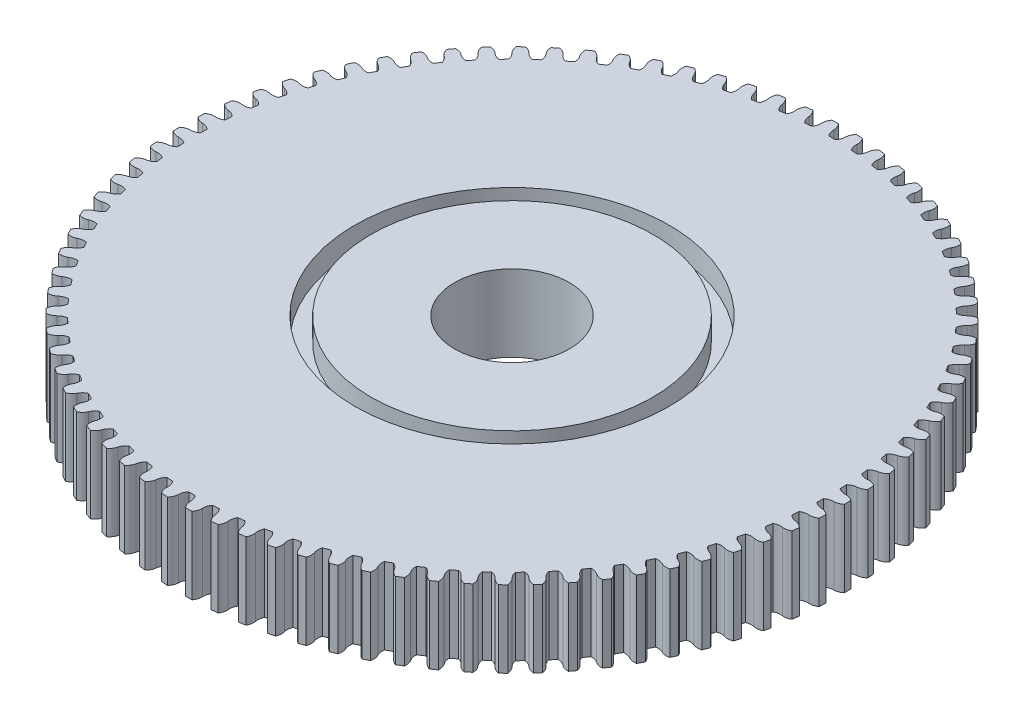
SolidWorks part; units mm, degrees
material "AISI 304"
ref_plane "Alzado" through (0, 0, 0) normal (0, 0, 1) x (1, 0, 0)
ref_plane "Planta" through (0, 0, 0) normal (0, 1, 0) x (1, 0, 0)
ref_plane "Vista lateral" through (0, 0, 0) normal (1, 0, 0) x (0, 0, -1)
sketch "Croquis1" plane through (0, 0, 0) normal (0, 1, 0) x (1, 0, 0)
  circle A0 centre (0, 0) radius 43
  dimension "D1" = 86
extrude "Saliente-Extruir1" add sketch "Croquis1" along normal blind 10
sketch "Croquis2" plane through (0, 10, 0) normal (0, 1, 0) x (1, 0, 0)
  line L0 (0, 0) -> (0, 42) construction
  arc A0 (1.9901, 42.9539) -> (-0.3825, 42.9983) centre (0, 0) ccw
  arc A2 (1.1967, 40.9825) -> (0.3366, 40.9986) centre (0, 0) ccw
  arc A3 (0, 42) -> (-0.3825, 42.9983) centre (-1.5705, 41.9706) ccw
  arc A5 (0, 42) -> (0.3366, 40.9986) centre (1.5705, 41.9706) ccw
  arc A6 (1.9901, 42.9539) -> (1.5705, 41.9706) centre (3.1388, 41.8825) ccw
  arc A7 (5.1945, 42.6851) -> (2.8318, 42.9067) centre (0, 0) ccw
  arc A8 (1.1967, 40.9825) -> (1.5705, 41.9706) centre (0, 42) ccw
  arc A9 (3.1387, 41.8826) -> (2.8318, 42.9067) centre (1.5703, 41.9706) ccw
  arc A10 (3.1387, 41.8826) -> (3.3995, 40.8588) centre (4.7026, 41.7359) ccw
  arc A11 (4.256, 40.7785) -> (3.3995, 40.8588) centre (0, 0) ccw
  arc A12 (4.256, 40.7785) -> (4.7026, 41.7359) centre (3.1387, 41.8826) ccw
  arc A13 (5.1945, 42.6851) -> (4.7026, 41.7359) centre (6.26, 41.5309) ccw
  arc A14 (8.3698, 42.1775) -> (6.0303, 42.5751) centre (0, 0) ccw
  arc A15 (6.2598, 41.5309) -> (6.0303, 42.5751) centre (4.7024, 41.7359) ccw
  arc A16 (6.2598, 41.5309) -> (6.4434, 40.4905) centre (7.8084, 41.2678) ccw
  arc A17 (7.2915, 40.3464) -> (6.4434, 40.4905) centre (0, 0) ccw
  arc A18 (7.2915, 40.3464) -> (7.8084, 41.2678) centre (6.2598, 41.5309) ccw
  arc A19 (8.3698, 42.1775) -> (7.8084, 41.2678) centre (9.3461, 40.9469) ccw
  arc A20 (11.4984, 41.4341) -> (9.1951, 42.0054) centre (0, 0) ccw
  arc A21 (9.3459, 40.947) -> (9.1951, 42.0054) centre (7.8082, 41.2678) ccw
  arc A22 (9.3459, 40.947) -> (9.4512, 39.8958) centre (10.8705, 40.5689) ccw
  arc A23 (10.2862, 39.6887) -> (9.4512, 39.8958) centre (0, 0) ccw
  arc A24 (10.2862, 39.6887) -> (10.8705, 40.5689) centre (9.3459, 40.947) ccw
  arc A25 (11.4984, 41.4341) -> (10.8705, 40.5689) centre (12.3799, 40.134) ccw
  arc A26 (14.5626, 40.459) -> (12.3084, 41.2008) centre (0, 0) ccw
  arc A27 (12.3797, 40.1341) -> (12.3084, 41.2008) centre (10.8703, 40.5689) ccw
  arc A28 (12.3797, 40.1341) -> (12.4062, 39.078) centre (13.8718, 39.6431) ccw
  arc A29 (13.2234, 38.8091) -> (12.4062, 39.078) centre (0, 0) ccw
  arc A30 (13.2234, 38.8091) -> (13.8718, 39.6431) centre (12.3797, 40.1341) ccw
  arc A31 (14.5626, 40.459) -> (13.8718, 39.6431) centre (15.3445, 39.0966) ccw
  arc A32 (17.5454, 39.2576) -> (15.3529, 40.1657) centre (0, 0) ccw
  arc A33 (15.3443, 39.0967) -> (15.3529, 40.1657) centre (13.8716, 39.6431) ccw
  arc A34 (15.3443, 39.0967) -> (15.2918, 38.0416) centre (16.7955, 38.4956) ccw
  arc A35 (16.0866, 37.7123) -> (15.2918, 38.0416) centre (0, 0) ccw
  arc A36 (16.0866, 37.7123) -> (16.7955, 38.4956) centre (15.3443, 39.0967) ccw
  arc A37 (17.5454, 39.2576) -> (16.7955, 38.4956) centre (18.2233, 37.8406) ccw
  arc A38 (20.4301, 37.8367) -> (18.3116, 38.9061) centre (0, 0) ccw
  arc A39 (18.2231, 37.8407) -> (18.3116, 38.9061) centre (16.7954, 38.4957) ccw
  arc A40 (18.2231, 37.8407) -> (18.0919, 36.7924) centre (19.6254, 37.1328) ccw
  arc A41 (18.8599, 36.4047) -> (18.0919, 36.7924) centre (0, 0) ccw
  arc A42 (18.8599, 36.4047) -> (19.6254, 37.1328) centre (18.2231, 37.8407) ccw
  arc A43 (20.4301, 37.8367) -> (19.6254, 37.1328) centre (21.0002, 36.373) ccw
  arc A44 (23.2005, 36.2041) -> (21.1679, 37.4289) centre (0, 0) ccw
  arc A45 (21, 36.3731) -> (21.1679, 37.4289) centre (19.6252, 37.1329) ccw
  arc A46 (21, 36.3731) -> (20.7908, 35.3376) centre (22.3454, 35.5624) ccw
  arc A47 (21.5277, 34.8935) -> (20.7908, 35.3376) centre (0, 0) ccw
  arc A48 (21.5277, 34.8935) -> (22.3454, 35.5624) centre (21, 36.3731) ccw
  arc A49 (23.2005, 36.2041) -> (22.3454, 35.5624) centre (23.6596, 34.7019) ccw
  arc A50 (25.8411, 34.3691) -> (23.9057, 35.7424) centre (0, 0) ccw
  arc A51 (23.6594, 34.702) -> (23.9057, 35.7424) centre (22.3453, 35.5625) ccw
  arc A52 (23.6594, 34.702) -> (23.3734, 33.685) centre (24.9405, 33.7931) ccw
  arc A53 (24.0751, 33.1872) -> (23.3734, 33.685) centre (0, 0) ccw
  arc A54 (24.0751, 33.1872) -> (24.9405, 33.7931) centre (23.6594, 34.702) ccw
  arc A55 (25.8411, 34.3691) -> (24.9405, 33.7931) centre (26.1867, 32.8368) ccw
  arc A56 (28.3373, 32.3419) -> (26.5099, 33.8559) centre (0, 0) ccw
  arc A57 (26.1866, 32.8369) -> (26.5099, 33.8559) centre (24.9404, 33.7932) ccw
  arc A58 (26.1866, 32.8369) -> (25.8254, 31.8442) centre (27.3961, 31.8348) ccw
  arc A59 (26.4878, 31.2953) -> (25.8254, 31.8442) centre (0, 0) ccw
  arc A60 (26.4878, 31.2953) -> (27.3961, 31.8348) centre (26.1866, 32.8369) ccw
  arc A61 (28.3373, 32.3419) -> (27.3961, 31.8348) centre (28.5674, 30.7881) ccw
  arc A62 (30.675, 30.1338) -> (28.9658, 31.7802) centre (0, 0) ccw
  arc A63 (28.5673, 30.7882) -> (28.9658, 31.7802) centre (27.396, 31.8349) ccw
  arc A64 (28.5673, 30.7882) -> (28.1329, 29.8252) centre (29.6985, 29.6984) ccw
  arc A65 (28.7525, 29.2283) -> (28.1329, 29.8252) centre (0, 0) ccw
  arc A66 (28.7525, 29.2283) -> (29.6985, 29.6984) centre (28.5673, 30.7882) ccw
  arc A67 (30.675, 30.1338) -> (29.6985, 29.6984) centre (30.7883, 28.5671) ccw
  arc A68 (32.8411, 27.7572) -> (31.2598, 29.5267) centre (0, 0) ccw
  arc A69 (30.7882, 28.5673) -> (31.2598, 29.5267) centre (29.6984, 29.6985) ccw
  arc A70 (30.7882, 28.5673) -> (30.283, 27.6394) centre (31.8349, 27.396) ccw
  arc A71 (30.8563, 26.9979) -> (30.283, 27.6394) centre (0, 0) ccw
  arc A72 (30.8563, 26.9979) -> (31.8349, 27.396) centre (30.7882, 28.5673) ccw
  arc A73 (32.8411, 27.7572) -> (31.8349, 27.396) centre (32.837, 26.1864) ccw
  arc A74 (34.8236, 25.2254) -> (33.3789, 27.1081) centre (0, 0) ccw
  arc A75 (32.8369, 26.1866) -> (33.3789, 27.1081) centre (31.8348, 27.3961) ccw
  arc A76 (32.8369, 26.1866) -> (32.2639, 25.2991) centre (33.7932, 24.9404) ccw
  arc A77 (32.7876, 24.6166) -> (32.2639, 25.2991) centre (0, 0) ccw
  arc A78 (32.7876, 24.6166) -> (33.7932, 24.9404) centre (32.8369, 26.1866) ccw
  arc A79 (34.8236, 25.2254) -> (33.7932, 24.9404) centre (34.7021, 23.6593) ccw
  arc A80 (36.6113, 22.5525) -> (35.3114, 24.5379) centre (0, 0) ccw
  arc A81 (34.702, 23.6594) -> (35.3114, 24.5379) centre (33.7931, 24.9405) ccw
  arc A82 (34.702, 23.6594) -> (34.0643, 22.8172) centre (35.5625, 22.3453) ccw
  arc A83 (34.5355, 22.0975) -> (34.0643, 22.8172) centre (0, 0) ccw
  arc A84 (34.5355, 22.0975) -> (35.5625, 22.3453) centre (34.702, 23.6594) ccw
  arc A85 (36.6113, 22.5525) -> (35.5625, 22.3453) centre (36.3732, 20.9998) ccw
  arc A86 (38.1943, 19.7535) -> (37.0463, 21.8304) centre (0, 0) ccw
  arc A87 (36.3731, 21) -> (37.0463, 21.8304) centre (35.5624, 22.3454) ccw
  arc A88 (36.3731, 21) -> (35.6741, 20.2078) centre (37.1329, 19.6252) ccw
  arc A89 (36.0903, 19.4549) -> (35.6741, 20.2078) centre (0, 0) ccw
  arc A90 (36.0903, 19.4549) -> (37.1329, 19.6252) centre (36.3731, 21) ccw
  arc A91 (38.1943, 19.7535) -> (37.1329, 19.6252) centre (37.8408, 18.223) ccw
  arc A92 (39.5636, 16.844) -> (38.5741, 19.0009) centre (0, 0) ccw
  arc A93 (37.8407, 18.2231) -> (38.5741, 19.0009) centre (37.1328, 19.6254) ccw
  arc A94 (37.8407, 18.2231) -> (37.0845, 17.4854) centre (38.4957, 16.7954) ccw
  arc A95 (37.4432, 16.7034) -> (37.0845, 17.4854) centre (0, 0) ccw
  arc A96 (37.4432, 16.7034) -> (38.4957, 16.7954) centre (37.8407, 18.2231) ccw
  arc A97 (39.5636, 16.844) -> (38.4957, 16.7954) centre (39.0968, 15.3442) ccw
  arc A98 (40.7118, 13.8403) -> (39.8862, 16.0651) centre (0, 0) ccw
  arc A99 (39.0967, 15.3443) -> (39.8862, 16.0651) centre (38.4956, 16.7955) ccw
  arc A100 (39.0967, 15.3443) -> (38.2875, 14.6652) centre (39.6431, 13.8716) ccw
  arc A101 (38.5868, 13.8586) -> (38.2875, 14.6652) centre (0, 0) ccw
  arc A102 (38.5868, 13.8586) -> (39.6431, 13.8716) centre (39.0967, 15.3443) ccw
  arc A103 (40.7118, 13.8403) -> (39.6431, 13.8716) centre (40.1341, 12.3795) ccw
  arc A104 (41.6322, 10.7592) -> (40.9752, 13.0395) centre (0, 0) ccw
  arc A105 (40.1341, 12.3797) -> (40.9752, 13.0395) centre (39.6431, 13.8718) ccw
  arc A106 (40.1341, 12.3797) -> (39.2764, 11.7629) centre (40.5689, 10.8703) ccw
  arc A107 (39.5145, 10.9363) -> (39.2764, 11.7629) centre (0, 0) ccw
  arc A108 (39.5145, 10.9363) -> (40.5689, 10.8703) centre (40.1341, 12.3797) ccw
  arc A109 (41.6322, 10.7592) -> (40.5689, 10.8703) centre (40.947, 9.3457) ccw
  arc A110 (42.3198, 7.6179) -> (41.8351, 9.941) centre (0, 0) ccw
  arc A111 (40.947, 9.3459) -> (41.8351, 9.941) centre (40.5689, 10.8705) ccw
  arc A112 (40.947, 9.3459) -> (40.0456, 8.7949) centre (41.2678, 7.8082) ccw
  arc A113 (40.2213, 7.9527) -> (40.0456, 8.7949) centre (0, 0) ccw
  arc A114 (40.2213, 7.9527) -> (41.2678, 7.8082) centre (40.947, 9.3459) ccw
  arc A115 (42.3198, 7.6179) -> (41.2678, 7.8082) centre (41.5309, 6.2596) ccw
  arc A116 (42.7708, 4.4341) -> (42.461, 6.7868) centre (0, 0) ccw
  arc A117 (41.5309, 6.2598) -> (42.461, 6.7868) centre (41.2678, 7.8084) ccw
  arc A118 (41.5309, 6.2598) -> (40.5909, 5.7777) centre (41.7359, 4.7024) ccw
  arc A119 (40.7032, 4.9248) -> (40.5909, 5.7777) centre (0, 0) ccw
  arc A120 (40.7032, 4.9248) -> (41.7359, 4.7024) centre (41.5309, 6.2598) ccw
  arc A121 (42.7708, 4.4341) -> (41.7359, 4.7024) centre (41.8826, 3.1385) ccw
  arc A122 (42.9825, 1.2254) -> (42.8495, 3.5947) centre (0, 0) ccw
  arc A123 (41.8826, 3.1387) -> (42.8495, 3.5947) centre (41.7359, 4.7026) ccw
  arc A124 (41.8826, 3.1387) -> (40.9091, 2.7282) centre (41.9706, 1.5703) ccw
  arc A125 (40.9574, 1.8692) -> (40.9091, 2.7282) centre (0, 0) ccw
  arc A126 (40.9574, 1.8692) -> (41.9706, 1.5703) centre (41.8826, 3.1387) ccw
  arc A127 (42.9825, 1.2254) -> (41.9706, 1.5703) centre (42, -0.0002) ccw
  arc A128 (42.9539, -1.9901) -> (42.9983, 0.3825) centre (0, 0) ccw
  arc A129 (42, 0) -> (42.9983, 0.3825) centre (41.9706, 1.5705) ccw
  arc A130 (42, 0) -> (40.9986, -0.3366) centre (41.9706, -1.5705) ccw
  arc A131 (40.9825, -1.1967) -> (40.9986, -0.3366) centre (0, 0) ccw
  arc A132 (40.9825, -1.1967) -> (41.9706, -1.5705) centre (42, 0) ccw
  arc A133 (42.9539, -1.9901) -> (41.9706, -1.5705) centre (41.8825, -3.1388) ccw
  arc A134 (42.6851, -5.1945) -> (42.9067, -2.8318) centre (0, 0) ccw
  arc A135 (41.8826, -3.1387) -> (42.9067, -2.8318) centre (41.9706, -1.5703) ccw
  arc A136 (41.8826, -3.1387) -> (40.8588, -3.3995) centre (41.7359, -4.7026) ccw
  arc A137 (40.7785, -4.256) -> (40.8588, -3.3995) centre (0, 0) ccw
  arc A138 (40.7785, -4.256) -> (41.7359, -4.7026) centre (41.8826, -3.1387) ccw
  arc A139 (42.6851, -5.1945) -> (41.7359, -4.7026) centre (41.5309, -6.26) ccw
  arc A140 (42.1775, -8.3698) -> (42.5751, -6.0303) centre (0, 0) ccw
  arc A141 (41.5309, -6.2598) -> (42.5751, -6.0303) centre (41.7359, -4.7024) ccw
  arc A142 (41.5309, -6.2598) -> (40.4905, -6.4434) centre (41.2678, -7.8084) ccw
  arc A143 (40.3464, -7.2915) -> (40.4905, -6.4434) centre (0, 0) ccw
  arc A144 (40.3464, -7.2915) -> (41.2678, -7.8084) centre (41.5309, -6.2598) ccw
  arc A145 (42.1775, -8.3698) -> (41.2678, -7.8084) centre (40.9469, -9.3461) ccw
  arc A146 (41.4341, -11.4984) -> (42.0054, -9.1951) centre (0, 0) ccw
  arc A147 (40.947, -9.3459) -> (42.0054, -9.1951) centre (41.2678, -7.8082) ccw
  arc A148 (40.947, -9.3459) -> (39.8958, -9.4512) centre (40.5689, -10.8705) ccw
  arc A149 (39.6887, -10.2862) -> (39.8958, -9.4512) centre (0, 0) ccw
  arc A150 (39.6887, -10.2862) -> (40.5689, -10.8705) centre (40.947, -9.3459) ccw
  arc A151 (41.4341, -11.4984) -> (40.5689, -10.8705) centre (40.134, -12.3799) ccw
  arc A152 (40.459, -14.5626) -> (41.2008, -12.3084) centre (0, 0) ccw
  arc A153 (40.1341, -12.3797) -> (41.2008, -12.3084) centre (40.5689, -10.8703) ccw
  arc A154 (40.1341, -12.3797) -> (39.078, -12.4062) centre (39.6431, -13.8718) ccw
  arc A155 (38.8091, -13.2234) -> (39.078, -12.4062) centre (0, 0) ccw
  arc A156 (38.8091, -13.2234) -> (39.6431, -13.8718) centre (40.1341, -12.3797) ccw
  arc A157 (40.459, -14.5626) -> (39.6431, -13.8718) centre (39.0966, -15.3445) ccw
  arc A158 (39.2576, -17.5454) -> (40.1657, -15.3529) centre (0, 0) ccw
  arc A159 (39.0967, -15.3443) -> (40.1657, -15.3529) centre (39.6431, -13.8716) ccw
  arc A160 (39.0967, -15.3443) -> (38.0416, -15.2918) centre (38.4956, -16.7955) ccw
  arc A161 (37.7123, -16.0866) -> (38.0416, -15.2918) centre (0, 0) ccw
  arc A162 (37.7123, -16.0866) -> (38.4956, -16.7955) centre (39.0967, -15.3443) ccw
  arc A163 (39.2576, -17.5454) -> (38.4956, -16.7955) centre (37.8406, -18.2233) ccw
  arc A164 (37.8367, -20.4301) -> (38.9061, -18.3116) centre (0, 0) ccw
  arc A165 (37.8407, -18.2231) -> (38.9061, -18.3116) centre (38.4957, -16.7954) ccw
  arc A166 (37.8407, -18.2231) -> (36.7924, -18.0919) centre (37.1328, -19.6254) ccw
  arc A167 (36.4047, -18.8599) -> (36.7924, -18.0919) centre (0, 0) ccw
  arc A168 (36.4047, -18.8599) -> (37.1328, -19.6254) centre (37.8407, -18.2231) ccw
  arc A169 (37.8367, -20.4301) -> (37.1328, -19.6254) centre (36.373, -21.0002) ccw
  arc A170 (36.2041, -23.2005) -> (37.4289, -21.1679) centre (0, 0) ccw
  arc A171 (36.3731, -21) -> (37.4289, -21.1679) centre (37.1329, -19.6252) ccw
  arc A172 (36.3731, -21) -> (35.3376, -20.7908) centre (35.5624, -22.3454) ccw
  arc A173 (34.8935, -21.5277) -> (35.3376, -20.7908) centre (0, 0) ccw
  arc A174 (34.8935, -21.5277) -> (35.5624, -22.3454) centre (36.3731, -21) ccw
  arc A175 (36.2041, -23.2005) -> (35.5624, -22.3454) centre (34.7019, -23.6596) ccw
  arc A176 (34.3691, -25.8411) -> (35.7424, -23.9057) centre (0, 0) ccw
  arc A177 (34.702, -23.6594) -> (35.7424, -23.9057) centre (35.5625, -22.3453) ccw
  arc A178 (34.702, -23.6594) -> (33.685, -23.3734) centre (33.7931, -24.9405) ccw
  arc A179 (33.1872, -24.0751) -> (33.685, -23.3734) centre (0, 0) ccw
  arc A180 (33.1872, -24.0751) -> (33.7931, -24.9405) centre (34.702, -23.6594) ccw
  arc A181 (34.3691, -25.8411) -> (33.7931, -24.9405) centre (32.8368, -26.1867) ccw
  arc A182 (32.3419, -28.3373) -> (33.8559, -26.5099) centre (0, 0) ccw
  arc A183 (32.8369, -26.1866) -> (33.8559, -26.5099) centre (33.7932, -24.9404) ccw
  arc A184 (32.8369, -26.1866) -> (31.8442, -25.8254) centre (31.8348, -27.3961) ccw
  arc A185 (31.2953, -26.4878) -> (31.8442, -25.8254) centre (0, 0) ccw
  arc A186 (31.2953, -26.4878) -> (31.8348, -27.3961) centre (32.8369, -26.1866) ccw
  arc A187 (32.3419, -28.3373) -> (31.8348, -27.3961) centre (30.7881, -28.5674) ccw
  arc A188 (30.1338, -30.675) -> (31.7802, -28.9658) centre (0, 0) ccw
  arc A189 (30.7882, -28.5673) -> (31.7802, -28.9658) centre (31.8349, -27.396) ccw
  arc A190 (30.7882, -28.5673) -> (29.8252, -28.1329) centre (29.6984, -29.6985) ccw
  arc A191 (29.2283, -28.7525) -> (29.8252, -28.1329) centre (0, 0) ccw
  arc A192 (29.2283, -28.7525) -> (29.6984, -29.6985) centre (30.7882, -28.5673) ccw
  arc A193 (30.1338, -30.675) -> (29.6984, -29.6985) centre (28.5671, -30.7883) ccw
  arc A194 (27.7572, -32.8411) -> (29.5267, -31.2598) centre (0, 0) ccw
  arc A195 (28.5673, -30.7882) -> (29.5267, -31.2598) centre (29.6985, -29.6984) ccw
  arc A196 (28.5673, -30.7882) -> (27.6394, -30.283) centre (27.396, -31.8349) ccw
  arc A197 (26.9979, -30.8563) -> (27.6394, -30.283) centre (0, 0) ccw
  arc A198 (26.9979, -30.8563) -> (27.396, -31.8349) centre (28.5673, -30.7882) ccw
  arc A199 (27.7572, -32.8411) -> (27.396, -31.8349) centre (26.1864, -32.837) ccw
  arc A200 (25.2254, -34.8236) -> (27.1081, -33.3789) centre (0, 0) ccw
  arc A201 (26.1866, -32.8369) -> (27.1081, -33.3789) centre (27.3961, -31.8348) ccw
  arc A202 (26.1866, -32.8369) -> (25.2991, -32.2639) centre (24.9404, -33.7932) ccw
  arc A203 (24.6166, -32.7876) -> (25.2991, -32.2639) centre (0, 0) ccw
  arc A204 (24.6166, -32.7876) -> (24.9404, -33.7932) centre (26.1866, -32.8369) ccw
  arc A205 (25.2254, -34.8236) -> (24.9404, -33.7932) centre (23.6593, -34.7021) ccw
  arc A206 (22.5525, -36.6113) -> (24.5379, -35.3114) centre (0, 0) ccw
  arc A207 (23.6594, -34.702) -> (24.5379, -35.3114) centre (24.9405, -33.7931) ccw
  arc A208 (23.6594, -34.702) -> (22.8172, -34.0643) centre (22.3453, -35.5625) ccw
  arc A209 (22.0975, -34.5355) -> (22.8172, -34.0643) centre (0, 0) ccw
  arc A210 (22.0975, -34.5355) -> (22.3453, -35.5625) centre (23.6594, -34.702) ccw
  arc A211 (22.5525, -36.6113) -> (22.3453, -35.5625) centre (20.9998, -36.3732) ccw
  arc A212 (19.7535, -38.1943) -> (21.8304, -37.0463) centre (0, 0) ccw
  arc A213 (21, -36.3731) -> (21.8304, -37.0463) centre (22.3454, -35.5624) ccw
  arc A214 (21, -36.3731) -> (20.2078, -35.6741) centre (19.6252, -37.1329) ccw
  arc A215 (19.4549, -36.0903) -> (20.2078, -35.6741) centre (0, 0) ccw
  arc A216 (19.4549, -36.0903) -> (19.6252, -37.1329) centre (21, -36.3731) ccw
  arc A217 (19.7535, -38.1943) -> (19.6252, -37.1329) centre (18.223, -37.8408) ccw
  arc A218 (16.844, -39.5636) -> (19.0009, -38.5741) centre (0, 0) ccw
  arc A219 (18.2231, -37.8407) -> (19.0009, -38.5741) centre (19.6254, -37.1328) ccw
  arc A220 (18.2231, -37.8407) -> (17.4854, -37.0845) centre (16.7954, -38.4957) ccw
  arc A221 (16.7034, -37.4432) -> (17.4854, -37.0845) centre (0, 0) ccw
  arc A222 (16.7034, -37.4432) -> (16.7954, -38.4957) centre (18.2231, -37.8407) ccw
  arc A223 (16.844, -39.5636) -> (16.7954, -38.4957) centre (15.3442, -39.0968) ccw
  arc A224 (13.8403, -40.7118) -> (16.0651, -39.8862) centre (0, 0) ccw
  arc A225 (15.3443, -39.0967) -> (16.0651, -39.8862) centre (16.7955, -38.4956) ccw
  arc A226 (15.3443, -39.0967) -> (14.6652, -38.2875) centre (13.8716, -39.6431) ccw
  arc A227 (13.8586, -38.5868) -> (14.6652, -38.2875) centre (0, 0) ccw
  arc A228 (13.8586, -38.5868) -> (13.8716, -39.6431) centre (15.3443, -39.0967) ccw
  arc A229 (13.8403, -40.7118) -> (13.8716, -39.6431) centre (12.3795, -40.1341) ccw
  arc A230 (10.7592, -41.6322) -> (13.0395, -40.9752) centre (0, 0) ccw
  arc A231 (12.3797, -40.1341) -> (13.0395, -40.9752) centre (13.8718, -39.6431) ccw
  arc A232 (12.3797, -40.1341) -> (11.7629, -39.2764) centre (10.8703, -40.5689) ccw
  arc A233 (10.9363, -39.5145) -> (11.7629, -39.2764) centre (0, 0) ccw
  arc A234 (10.9363, -39.5145) -> (10.8703, -40.5689) centre (12.3797, -40.1341) ccw
  arc A235 (10.7592, -41.6322) -> (10.8703, -40.5689) centre (9.3457, -40.947) ccw
  arc A236 (7.6179, -42.3198) -> (9.941, -41.8351) centre (0, 0) ccw
  arc A237 (9.3459, -40.947) -> (9.941, -41.8351) centre (10.8705, -40.5689) ccw
  arc A238 (9.3459, -40.947) -> (8.7949, -40.0456) centre (7.8082, -41.2678) ccw
  arc A239 (7.9527, -40.2213) -> (8.7949, -40.0456) centre (0, 0) ccw
  arc A240 (7.9527, -40.2213) -> (7.8082, -41.2678) centre (9.3459, -40.947) ccw
  arc A241 (7.6179, -42.3198) -> (7.8082, -41.2678) centre (6.2596, -41.5309) ccw
  arc A242 (4.4341, -42.7708) -> (6.7868, -42.461) centre (0, 0) ccw
  arc A243 (6.2598, -41.5309) -> (6.7868, -42.461) centre (7.8084, -41.2678) ccw
  arc A244 (6.2598, -41.5309) -> (5.7777, -40.5909) centre (4.7024, -41.7359) ccw
  arc A245 (4.9248, -40.7032) -> (5.7777, -40.5909) centre (0, 0) ccw
  arc A246 (4.9248, -40.7032) -> (4.7024, -41.7359) centre (6.2598, -41.5309) ccw
  arc A247 (4.4341, -42.7708) -> (4.7024, -41.7359) centre (3.1385, -41.8826) ccw
  arc A248 (1.2254, -42.9825) -> (3.5947, -42.8495) centre (0, 0) ccw
  arc A249 (3.1387, -41.8826) -> (3.5947, -42.8495) centre (4.7026, -41.7359) ccw
  arc A250 (3.1387, -41.8826) -> (2.7282, -40.9091) centre (1.5703, -41.9706) ccw
  arc A251 (1.8692, -40.9574) -> (2.7282, -40.9091) centre (0, 0) ccw
  arc A252 (1.8692, -40.9574) -> (1.5703, -41.9706) centre (3.1387, -41.8826) ccw
  arc A253 (1.2254, -42.9825) -> (1.5703, -41.9706) centre (-0.0002, -42) ccw
  arc A254 (-1.9901, -42.9539) -> (0.3825, -42.9983) centre (0, 0) ccw
  arc A255 (0, -42) -> (0.3825, -42.9983) centre (1.5705, -41.9706) ccw
  arc A256 (0, -42) -> (-0.3366, -40.9986) centre (-1.5705, -41.9706) ccw
  arc A257 (-1.1967, -40.9825) -> (-0.3366, -40.9986) centre (0, 0) ccw
  arc A258 (-1.1967, -40.9825) -> (-1.5705, -41.9706) centre (0, -42) ccw
  arc A259 (-1.9901, -42.9539) -> (-1.5705, -41.9706) centre (-3.1388, -41.8825) ccw
  arc A260 (-5.1945, -42.6851) -> (-2.8318, -42.9067) centre (0, 0) ccw
  arc A261 (-3.1387, -41.8826) -> (-2.8318, -42.9067) centre (-1.5703, -41.9706) ccw
  arc A262 (-3.1387, -41.8826) -> (-3.3995, -40.8588) centre (-4.7026, -41.7359) ccw
  arc A263 (-4.256, -40.7785) -> (-3.3995, -40.8588) centre (0, 0) ccw
  arc A264 (-4.256, -40.7785) -> (-4.7026, -41.7359) centre (-3.1387, -41.8826) ccw
  arc A265 (-5.1945, -42.6851) -> (-4.7026, -41.7359) centre (-6.26, -41.5309) ccw
  arc A266 (-8.3698, -42.1775) -> (-6.0303, -42.5751) centre (0, 0) ccw
  arc A267 (-6.2598, -41.5309) -> (-6.0303, -42.5751) centre (-4.7024, -41.7359) ccw
  arc A268 (-6.2598, -41.5309) -> (-6.4434, -40.4905) centre (-7.8084, -41.2678) ccw
  arc A269 (-7.2915, -40.3464) -> (-6.4434, -40.4905) centre (0, 0) ccw
  arc A270 (-7.2915, -40.3464) -> (-7.8084, -41.2678) centre (-6.2598, -41.5309) ccw
  arc A271 (-8.3698, -42.1775) -> (-7.8084, -41.2678) centre (-9.3461, -40.9469) ccw
  arc A272 (-11.4984, -41.4341) -> (-9.1951, -42.0054) centre (0, 0) ccw
  arc A273 (-9.3459, -40.947) -> (-9.1951, -42.0054) centre (-7.8082, -41.2678) ccw
  arc A274 (-9.3459, -40.947) -> (-9.4512, -39.8958) centre (-10.8705, -40.5689) ccw
  arc A275 (-10.2862, -39.6887) -> (-9.4512, -39.8958) centre (0, 0) ccw
  arc A276 (-10.2862, -39.6887) -> (-10.8705, -40.5689) centre (-9.3459, -40.947) ccw
  arc A277 (-11.4984, -41.4341) -> (-10.8705, -40.5689) centre (-12.3799, -40.134) ccw
  arc A278 (-14.5626, -40.459) -> (-12.3084, -41.2008) centre (0, 0) ccw
  arc A279 (-12.3797, -40.1341) -> (-12.3084, -41.2008) centre (-10.8703, -40.5689) ccw
  arc A280 (-12.3797, -40.1341) -> (-12.4062, -39.078) centre (-13.8718, -39.6431) ccw
  arc A281 (-13.2234, -38.8091) -> (-12.4062, -39.078) centre (0, 0) ccw
  arc A282 (-13.2234, -38.8091) -> (-13.8718, -39.6431) centre (-12.3797, -40.1341) ccw
  arc A283 (-14.5626, -40.459) -> (-13.8718, -39.6431) centre (-15.3445, -39.0966) ccw
  arc A284 (-17.5454, -39.2576) -> (-15.3529, -40.1657) centre (0, 0) ccw
  arc A285 (-15.3443, -39.0967) -> (-15.3529, -40.1657) centre (-13.8716, -39.6431) ccw
  arc A286 (-15.3443, -39.0967) -> (-15.2918, -38.0416) centre (-16.7955, -38.4956) ccw
  arc A287 (-16.0866, -37.7123) -> (-15.2918, -38.0416) centre (0, 0) ccw
  arc A288 (-16.0866, -37.7123) -> (-16.7955, -38.4956) centre (-15.3443, -39.0967) ccw
  arc A289 (-17.5454, -39.2576) -> (-16.7955, -38.4956) centre (-18.2233, -37.8406) ccw
  arc A290 (-20.4301, -37.8367) -> (-18.3116, -38.9061) centre (0, 0) ccw
  arc A291 (-18.2231, -37.8407) -> (-18.3116, -38.9061) centre (-16.7954, -38.4957) ccw
  arc A292 (-18.2231, -37.8407) -> (-18.0919, -36.7924) centre (-19.6254, -37.1328) ccw
  arc A293 (-18.8599, -36.4047) -> (-18.0919, -36.7924) centre (0, 0) ccw
  arc A294 (-18.8599, -36.4047) -> (-19.6254, -37.1328) centre (-18.2231, -37.8407) ccw
  arc A295 (-20.4301, -37.8367) -> (-19.6254, -37.1328) centre (-21.0002, -36.373) ccw
  arc A296 (-23.2005, -36.2041) -> (-21.1679, -37.4289) centre (0, 0) ccw
  arc A297 (-21, -36.3731) -> (-21.1679, -37.4289) centre (-19.6252, -37.1329) ccw
  arc A298 (-21, -36.3731) -> (-20.7908, -35.3376) centre (-22.3454, -35.5624) ccw
  arc A299 (-21.5277, -34.8935) -> (-20.7908, -35.3376) centre (0, 0) ccw
  arc A300 (-21.5277, -34.8935) -> (-22.3454, -35.5624) centre (-21, -36.3731) ccw
  arc A301 (-23.2005, -36.2041) -> (-22.3454, -35.5624) centre (-23.6596, -34.7019) ccw
  arc A302 (-25.8411, -34.3691) -> (-23.9057, -35.7424) centre (0, 0) ccw
  arc A303 (-23.6594, -34.702) -> (-23.9057, -35.7424) centre (-22.3453, -35.5625) ccw
  arc A304 (-23.6594, -34.702) -> (-23.3734, -33.685) centre (-24.9405, -33.7931) ccw
  arc A305 (-24.0751, -33.1872) -> (-23.3734, -33.685) centre (0, 0) ccw
  arc A306 (-24.0751, -33.1872) -> (-24.9405, -33.7931) centre (-23.6594, -34.702) ccw
  arc A307 (-25.8411, -34.3691) -> (-24.9405, -33.7931) centre (-26.1867, -32.8368) ccw
  arc A308 (-28.3373, -32.3419) -> (-26.5099, -33.8559) centre (0, 0) ccw
  arc A309 (-26.1866, -32.8369) -> (-26.5099, -33.8559) centre (-24.9404, -33.7932) ccw
  arc A310 (-26.1866, -32.8369) -> (-25.8254, -31.8442) centre (-27.3961, -31.8348) ccw
  arc A311 (-26.4878, -31.2953) -> (-25.8254, -31.8442) centre (0, 0) ccw
  arc A312 (-26.4878, -31.2953) -> (-27.3961, -31.8348) centre (-26.1866, -32.8369) ccw
  arc A313 (-28.3373, -32.3419) -> (-27.3961, -31.8348) centre (-28.5674, -30.7881) ccw
  arc A314 (-30.675, -30.1338) -> (-28.9658, -31.7802) centre (0, 0) ccw
  arc A315 (-28.5673, -30.7882) -> (-28.9658, -31.7802) centre (-27.396, -31.8349) ccw
  arc A316 (-28.5673, -30.7882) -> (-28.1329, -29.8252) centre (-29.6985, -29.6984) ccw
  arc A317 (-28.7525, -29.2283) -> (-28.1329, -29.8252) centre (0, 0) ccw
  arc A318 (-28.7525, -29.2283) -> (-29.6985, -29.6984) centre (-28.5673, -30.7882) ccw
  arc A319 (-30.675, -30.1338) -> (-29.6985, -29.6984) centre (-30.7883, -28.5671) ccw
  arc A320 (-32.8411, -27.7572) -> (-31.2598, -29.5267) centre (0, 0) ccw
  arc A321 (-30.7882, -28.5673) -> (-31.2598, -29.5267) centre (-29.6984, -29.6985) ccw
  arc A322 (-30.7882, -28.5673) -> (-30.283, -27.6394) centre (-31.8349, -27.396) ccw
  arc A323 (-30.8563, -26.9979) -> (-30.283, -27.6394) centre (0, 0) ccw
  arc A324 (-30.8563, -26.9979) -> (-31.8349, -27.396) centre (-30.7882, -28.5673) ccw
  arc A325 (-32.8411, -27.7572) -> (-31.8349, -27.396) centre (-32.837, -26.1864) ccw
  arc A326 (-34.8236, -25.2254) -> (-33.3789, -27.1081) centre (0, 0) ccw
  arc A327 (-32.8369, -26.1866) -> (-33.3789, -27.1081) centre (-31.8348, -27.3961) ccw
  arc A328 (-32.8369, -26.1866) -> (-32.2639, -25.2991) centre (-33.7932, -24.9404) ccw
  arc A329 (-32.7876, -24.6166) -> (-32.2639, -25.2991) centre (0, 0) ccw
  arc A330 (-32.7876, -24.6166) -> (-33.7932, -24.9404) centre (-32.8369, -26.1866) ccw
  arc A331 (-34.8236, -25.2254) -> (-33.7932, -24.9404) centre (-34.7021, -23.6593) ccw
  arc A332 (-36.6113, -22.5525) -> (-35.3114, -24.5379) centre (0, 0) ccw
  arc A333 (-34.702, -23.6594) -> (-35.3114, -24.5379) centre (-33.7931, -24.9405) ccw
  arc A334 (-34.702, -23.6594) -> (-34.0643, -22.8172) centre (-35.5625, -22.3453) ccw
  arc A335 (-34.5355, -22.0975) -> (-34.0643, -22.8172) centre (0, 0) ccw
  arc A336 (-34.5355, -22.0975) -> (-35.5625, -22.3453) centre (-34.702, -23.6594) ccw
  arc A337 (-36.6113, -22.5525) -> (-35.5625, -22.3453) centre (-36.3732, -20.9998) ccw
  arc A338 (-38.1943, -19.7535) -> (-37.0463, -21.8304) centre (0, 0) ccw
  arc A339 (-36.3731, -21) -> (-37.0463, -21.8304) centre (-35.5624, -22.3454) ccw
  arc A340 (-36.3731, -21) -> (-35.6741, -20.2078) centre (-37.1329, -19.6252) ccw
  arc A341 (-36.0903, -19.4549) -> (-35.6741, -20.2078) centre (0, 0) ccw
  arc A342 (-36.0903, -19.4549) -> (-37.1329, -19.6252) centre (-36.3731, -21) ccw
  arc A343 (-38.1943, -19.7535) -> (-37.1329, -19.6252) centre (-37.8408, -18.223) ccw
  arc A344 (-39.5636, -16.844) -> (-38.5741, -19.0009) centre (0, 0) ccw
  arc A345 (-37.8407, -18.2231) -> (-38.5741, -19.0009) centre (-37.1328, -19.6254) ccw
  arc A346 (-37.8407, -18.2231) -> (-37.0845, -17.4854) centre (-38.4957, -16.7954) ccw
  arc A347 (-37.4432, -16.7034) -> (-37.0845, -17.4854) centre (0, 0) ccw
  arc A348 (-37.4432, -16.7034) -> (-38.4957, -16.7954) centre (-37.8407, -18.2231) ccw
  arc A349 (-39.5636, -16.844) -> (-38.4957, -16.7954) centre (-39.0968, -15.3442) ccw
  arc A350 (-40.7118, -13.8403) -> (-39.8862, -16.0651) centre (0, 0) ccw
  arc A351 (-39.0967, -15.3443) -> (-39.8862, -16.0651) centre (-38.4956, -16.7955) ccw
  arc A352 (-39.0967, -15.3443) -> (-38.2875, -14.6652) centre (-39.6431, -13.8716) ccw
  arc A353 (-38.5868, -13.8586) -> (-38.2875, -14.6652) centre (0, 0) ccw
  arc A354 (-38.5868, -13.8586) -> (-39.6431, -13.8716) centre (-39.0967, -15.3443) ccw
  arc A355 (-40.7118, -13.8403) -> (-39.6431, -13.8716) centre (-40.1341, -12.3795) ccw
  arc A356 (-41.6322, -10.7592) -> (-40.9752, -13.0395) centre (0, 0) ccw
  arc A357 (-40.1341, -12.3797) -> (-40.9752, -13.0395) centre (-39.6431, -13.8718) ccw
  arc A358 (-40.1341, -12.3797) -> (-39.2764, -11.7629) centre (-40.5689, -10.8703) ccw
  arc A359 (-39.5145, -10.9363) -> (-39.2764, -11.7629) centre (0, 0) ccw
  arc A360 (-39.5145, -10.9363) -> (-40.5689, -10.8703) centre (-40.1341, -12.3797) ccw
  arc A361 (-41.6322, -10.7592) -> (-40.5689, -10.8703) centre (-40.947, -9.3457) ccw
  arc A362 (-42.3198, -7.6179) -> (-41.8351, -9.941) centre (0, 0) ccw
  arc A363 (-40.947, -9.3459) -> (-41.8351, -9.941) centre (-40.5689, -10.8705) ccw
  arc A364 (-40.947, -9.3459) -> (-40.0456, -8.7949) centre (-41.2678, -7.8082) ccw
  arc A365 (-40.2213, -7.9527) -> (-40.0456, -8.7949) centre (0, 0) ccw
  arc A366 (-40.2213, -7.9527) -> (-41.2678, -7.8082) centre (-40.947, -9.3459) ccw
  arc A367 (-42.3198, -7.6179) -> (-41.2678, -7.8082) centre (-41.5309, -6.2596) ccw
  arc A368 (-42.7708, -4.4341) -> (-42.461, -6.7868) centre (0, 0) ccw
  arc A369 (-41.5309, -6.2598) -> (-42.461, -6.7868) centre (-41.2678, -7.8084) ccw
  arc A370 (-41.5309, -6.2598) -> (-40.5909, -5.7777) centre (-41.7359, -4.7024) ccw
  arc A371 (-40.7032, -4.9248) -> (-40.5909, -5.7777) centre (0, 0) ccw
  arc A372 (-40.7032, -4.9248) -> (-41.7359, -4.7024) centre (-41.5309, -6.2598) ccw
  arc A373 (-42.7708, -4.4341) -> (-41.7359, -4.7024) centre (-41.8826, -3.1385) ccw
  arc A374 (-42.9825, -1.2254) -> (-42.8495, -3.5947) centre (0, 0) ccw
  arc A375 (-41.8826, -3.1387) -> (-42.8495, -3.5947) centre (-41.7359, -4.7026) ccw
  arc A376 (-41.8826, -3.1387) -> (-40.9091, -2.7282) centre (-41.9706, -1.5703) ccw
  arc A377 (-40.9574, -1.8692) -> (-40.9091, -2.7282) centre (0, 0) ccw
  arc A378 (-40.9574, -1.8692) -> (-41.9706, -1.5703) centre (-41.8826, -3.1387) ccw
  arc A379 (-42.9825, -1.2254) -> (-41.9706, -1.5703) centre (-42, 0.0002) ccw
  arc A380 (-42.9539, 1.9901) -> (-42.9983, -0.3825) centre (0, 0) ccw
  arc A381 (-42, 0) -> (-42.9983, -0.3825) centre (-41.9706, -1.5705) ccw
  arc A382 (-42, 0) -> (-40.9986, 0.3366) centre (-41.9706, 1.5705) ccw
  arc A383 (-40.9825, 1.1967) -> (-40.9986, 0.3366) centre (0, 0) ccw
  arc A384 (-40.9825, 1.1967) -> (-41.9706, 1.5705) centre (-42, 0) ccw
  arc A385 (-42.9539, 1.9901) -> (-41.9706, 1.5705) centre (-41.8825, 3.1388) ccw
  arc A386 (-42.6851, 5.1945) -> (-42.9067, 2.8318) centre (0, 0) ccw
  arc A387 (-41.8826, 3.1387) -> (-42.9067, 2.8318) centre (-41.9706, 1.5703) ccw
  arc A388 (-41.8826, 3.1387) -> (-40.8588, 3.3995) centre (-41.7359, 4.7026) ccw
  arc A389 (-40.7785, 4.256) -> (-40.8588, 3.3995) centre (0, 0) ccw
  arc A390 (-40.7785, 4.256) -> (-41.7359, 4.7026) centre (-41.8826, 3.1387) ccw
  arc A391 (-42.6851, 5.1945) -> (-41.7359, 4.7026) centre (-41.5309, 6.26) ccw
  arc A392 (-42.1775, 8.3698) -> (-42.5751, 6.0303) centre (0, 0) ccw
  arc A393 (-41.5309, 6.2598) -> (-42.5751, 6.0303) centre (-41.7359, 4.7024) ccw
  arc A394 (-41.5309, 6.2598) -> (-40.4905, 6.4434) centre (-41.2678, 7.8084) ccw
  arc A395 (-40.3464, 7.2915) -> (-40.4905, 6.4434) centre (0, 0) ccw
  arc A396 (-40.3464, 7.2915) -> (-41.2678, 7.8084) centre (-41.5309, 6.2598) ccw
  arc A397 (-42.1775, 8.3698) -> (-41.2678, 7.8084) centre (-40.9469, 9.3461) ccw
  arc A398 (-41.4341, 11.4984) -> (-42.0054, 9.1951) centre (0, 0) ccw
  arc A399 (-40.947, 9.3459) -> (-42.0054, 9.1951) centre (-41.2678, 7.8082) ccw
  arc A400 (-40.947, 9.3459) -> (-39.8958, 9.4512) centre (-40.5689, 10.8705) ccw
  arc A401 (-39.6887, 10.2862) -> (-39.8958, 9.4512) centre (0, 0) ccw
  arc A402 (-39.6887, 10.2862) -> (-40.5689, 10.8705) centre (-40.947, 9.3459) ccw
  arc A403 (-41.4341, 11.4984) -> (-40.5689, 10.8705) centre (-40.134, 12.3799) ccw
  arc A404 (-40.459, 14.5626) -> (-41.2008, 12.3084) centre (0, 0) ccw
  arc A405 (-40.1341, 12.3797) -> (-41.2008, 12.3084) centre (-40.5689, 10.8703) ccw
  arc A406 (-40.1341, 12.3797) -> (-39.078, 12.4062) centre (-39.6431, 13.8718) ccw
  arc A407 (-38.8091, 13.2234) -> (-39.078, 12.4062) centre (0, 0) ccw
  arc A408 (-38.8091, 13.2234) -> (-39.6431, 13.8718) centre (-40.1341, 12.3797) ccw
  arc A409 (-40.459, 14.5626) -> (-39.6431, 13.8718) centre (-39.0966, 15.3445) ccw
  arc A410 (-39.2576, 17.5454) -> (-40.1657, 15.3529) centre (0, 0) ccw
  arc A411 (-39.0967, 15.3443) -> (-40.1657, 15.3529) centre (-39.6431, 13.8716) ccw
  arc A412 (-39.0967, 15.3443) -> (-38.0416, 15.2918) centre (-38.4956, 16.7955) ccw
  arc A413 (-37.7123, 16.0866) -> (-38.0416, 15.2918) centre (0, 0) ccw
  arc A414 (-37.7123, 16.0866) -> (-38.4956, 16.7955) centre (-39.0967, 15.3443) ccw
  arc A415 (-39.2576, 17.5454) -> (-38.4956, 16.7955) centre (-37.8406, 18.2233) ccw
  arc A416 (-37.8367, 20.4301) -> (-38.9061, 18.3116) centre (0, 0) ccw
  arc A417 (-37.8407, 18.2231) -> (-38.9061, 18.3116) centre (-38.4957, 16.7954) ccw
  arc A418 (-37.8407, 18.2231) -> (-36.7924, 18.0919) centre (-37.1328, 19.6254) ccw
  arc A419 (-36.4047, 18.8599) -> (-36.7924, 18.0919) centre (0, 0) ccw
  arc A420 (-36.4047, 18.8599) -> (-37.1328, 19.6254) centre (-37.8407, 18.2231) ccw
  arc A421 (-37.8367, 20.4301) -> (-37.1328, 19.6254) centre (-36.373, 21.0002) ccw
  arc A422 (-36.2041, 23.2005) -> (-37.4289, 21.1679) centre (0, 0) ccw
  arc A423 (-36.3731, 21) -> (-37.4289, 21.1679) centre (-37.1329, 19.6252) ccw
  arc A424 (-36.3731, 21) -> (-35.3376, 20.7908) centre (-35.5624, 22.3454) ccw
  arc A425 (-34.8935, 21.5277) -> (-35.3376, 20.7908) centre (0, 0) ccw
  arc A426 (-34.8935, 21.5277) -> (-35.5624, 22.3454) centre (-36.3731, 21) ccw
  arc A427 (-36.2041, 23.2005) -> (-35.5624, 22.3454) centre (-34.7019, 23.6596) ccw
  arc A428 (-34.3691, 25.8411) -> (-35.7424, 23.9057) centre (0, 0) ccw
  arc A429 (-34.702, 23.6594) -> (-35.7424, 23.9057) centre (-35.5625, 22.3453) ccw
  arc A430 (-34.702, 23.6594) -> (-33.685, 23.3734) centre (-33.7931, 24.9405) ccw
  arc A431 (-33.1872, 24.0751) -> (-33.685, 23.3734) centre (0, 0) ccw
  arc A432 (-33.1872, 24.0751) -> (-33.7931, 24.9405) centre (-34.702, 23.6594) ccw
  arc A433 (-34.3691, 25.8411) -> (-33.7931, 24.9405) centre (-32.8368, 26.1867) ccw
  arc A434 (-32.3419, 28.3373) -> (-33.8559, 26.5099) centre (0, 0) ccw
  arc A435 (-32.8369, 26.1866) -> (-33.8559, 26.5099) centre (-33.7932, 24.9404) ccw
  arc A436 (-32.8369, 26.1866) -> (-31.8442, 25.8254) centre (-31.8348, 27.3961) ccw
  arc A437 (-31.2953, 26.4878) -> (-31.8442, 25.8254) centre (0, 0) ccw
  arc A438 (-31.2953, 26.4878) -> (-31.8348, 27.3961) centre (-32.8369, 26.1866) ccw
  arc A439 (-32.3419, 28.3373) -> (-31.8348, 27.3961) centre (-30.7881, 28.5674) ccw
  arc A440 (-30.1338, 30.675) -> (-31.7802, 28.9658) centre (0, 0) ccw
  arc A441 (-30.7882, 28.5673) -> (-31.7802, 28.9658) centre (-31.8349, 27.396) ccw
  arc A442 (-30.7882, 28.5673) -> (-29.8252, 28.1329) centre (-29.6984, 29.6985) ccw
  arc A443 (-29.2283, 28.7525) -> (-29.8252, 28.1329) centre (0, 0) ccw
  arc A444 (-29.2283, 28.7525) -> (-29.6984, 29.6985) centre (-30.7882, 28.5673) ccw
  arc A445 (-30.1338, 30.675) -> (-29.6984, 29.6985) centre (-28.5671, 30.7883) ccw
  arc A446 (-27.7572, 32.8411) -> (-29.5267, 31.2598) centre (0, 0) ccw
  arc A447 (-28.5673, 30.7882) -> (-29.5267, 31.2598) centre (-29.6985, 29.6984) ccw
  arc A448 (-28.5673, 30.7882) -> (-27.6394, 30.283) centre (-27.396, 31.8349) ccw
  arc A449 (-26.9979, 30.8563) -> (-27.6394, 30.283) centre (0, 0) ccw
  arc A450 (-26.9979, 30.8563) -> (-27.396, 31.8349) centre (-28.5673, 30.7882) ccw
  arc A451 (-27.7572, 32.8411) -> (-27.396, 31.8349) centre (-26.1864, 32.837) ccw
  arc A452 (-25.2254, 34.8236) -> (-27.1081, 33.3789) centre (0, 0) ccw
  arc A453 (-26.1866, 32.8369) -> (-27.1081, 33.3789) centre (-27.3961, 31.8348) ccw
  arc A454 (-26.1866, 32.8369) -> (-25.2991, 32.2639) centre (-24.9404, 33.7932) ccw
  arc A455 (-24.6166, 32.7876) -> (-25.2991, 32.2639) centre (0, 0) ccw
  arc A456 (-24.6166, 32.7876) -> (-24.9404, 33.7932) centre (-26.1866, 32.8369) ccw
  arc A457 (-25.2254, 34.8236) -> (-24.9404, 33.7932) centre (-23.6593, 34.7021) ccw
  arc A458 (-22.5525, 36.6113) -> (-24.5379, 35.3114) centre (0, 0) ccw
  arc A459 (-23.6594, 34.702) -> (-24.5379, 35.3114) centre (-24.9405, 33.7931) ccw
  arc A460 (-23.6594, 34.702) -> (-22.8172, 34.0643) centre (-22.3453, 35.5625) ccw
  arc A461 (-22.0975, 34.5355) -> (-22.8172, 34.0643) centre (0, 0) ccw
  arc A462 (-22.0975, 34.5355) -> (-22.3453, 35.5625) centre (-23.6594, 34.702) ccw
  arc A463 (-22.5525, 36.6113) -> (-22.3453, 35.5625) centre (-20.9998, 36.3732) ccw
  arc A464 (-19.7535, 38.1943) -> (-21.8304, 37.0463) centre (0, 0) ccw
  arc A465 (-21, 36.3731) -> (-21.8304, 37.0463) centre (-22.3454, 35.5624) ccw
  arc A466 (-21, 36.3731) -> (-20.2078, 35.6741) centre (-19.6252, 37.1329) ccw
  arc A467 (-19.4549, 36.0903) -> (-20.2078, 35.6741) centre (0, 0) ccw
  arc A468 (-19.4549, 36.0903) -> (-19.6252, 37.1329) centre (-21, 36.3731) ccw
  arc A469 (-19.7535, 38.1943) -> (-19.6252, 37.1329) centre (-18.223, 37.8408) ccw
  arc A470 (-16.844, 39.5636) -> (-19.0009, 38.5741) centre (0, 0) ccw
  arc A471 (-18.2231, 37.8407) -> (-19.0009, 38.5741) centre (-19.6254, 37.1328) ccw
  arc A472 (-18.2231, 37.8407) -> (-17.4854, 37.0845) centre (-16.7954, 38.4957) ccw
  arc A473 (-16.7034, 37.4432) -> (-17.4854, 37.0845) centre (0, 0) ccw
  arc A474 (-16.7034, 37.4432) -> (-16.7954, 38.4957) centre (-18.2231, 37.8407) ccw
  arc A475 (-16.844, 39.5636) -> (-16.7954, 38.4957) centre (-15.3442, 39.0968) ccw
  arc A476 (-13.8403, 40.7118) -> (-16.0651, 39.8862) centre (0, 0) ccw
  arc A477 (-15.3443, 39.0967) -> (-16.0651, 39.8862) centre (-16.7955, 38.4956) ccw
  arc A478 (-15.3443, 39.0967) -> (-14.6652, 38.2875) centre (-13.8716, 39.6431) ccw
  arc A479 (-13.8586, 38.5868) -> (-14.6652, 38.2875) centre (0, 0) ccw
  arc A480 (-13.8586, 38.5868) -> (-13.8716, 39.6431) centre (-15.3443, 39.0967) ccw
  arc A481 (-13.8403, 40.7118) -> (-13.8716, 39.6431) centre (-12.3795, 40.1341) ccw
  arc A482 (-10.7592, 41.6322) -> (-13.0395, 40.9752) centre (0, 0) ccw
  arc A483 (-12.3797, 40.1341) -> (-13.0395, 40.9752) centre (-13.8718, 39.6431) ccw
  arc A484 (-12.3797, 40.1341) -> (-11.7629, 39.2764) centre (-10.8703, 40.5689) ccw
  arc A485 (-10.9363, 39.5145) -> (-11.7629, 39.2764) centre (0, 0) ccw
  arc A486 (-10.9363, 39.5145) -> (-10.8703, 40.5689) centre (-12.3797, 40.1341) ccw
  arc A487 (-10.7592, 41.6322) -> (-10.8703, 40.5689) centre (-9.3457, 40.947) ccw
  arc A488 (-7.6179, 42.3198) -> (-9.941, 41.8351) centre (0, 0) ccw
  arc A489 (-9.3459, 40.947) -> (-9.941, 41.8351) centre (-10.8705, 40.5689) ccw
  arc A490 (-9.3459, 40.947) -> (-8.7949, 40.0456) centre (-7.8082, 41.2678) ccw
  arc A491 (-7.9527, 40.2213) -> (-8.7949, 40.0456) centre (0, 0) ccw
  arc A492 (-7.9527, 40.2213) -> (-7.8082, 41.2678) centre (-9.3459, 40.947) ccw
  arc A493 (-7.6179, 42.3198) -> (-7.8082, 41.2678) centre (-6.2596, 41.5309) ccw
  arc A494 (-4.4341, 42.7708) -> (-6.7868, 42.461) centre (0, 0) ccw
  arc A495 (-6.2598, 41.5309) -> (-6.7868, 42.461) centre (-7.8084, 41.2678) ccw
  arc A496 (-6.2598, 41.5309) -> (-5.7777, 40.5909) centre (-4.7024, 41.7359) ccw
  arc A497 (-4.9248, 40.7032) -> (-5.7777, 40.5909) centre (0, 0) ccw
  arc A498 (-4.9248, 40.7032) -> (-4.7024, 41.7359) centre (-6.2598, 41.5309) ccw
  arc A499 (-4.4341, 42.7708) -> (-4.7024, 41.7359) centre (-3.1385, 41.8826) ccw
  arc A500 (-1.2254, 42.9825) -> (-3.5947, 42.8495) centre (0, 0) ccw
  arc A501 (-3.1387, 41.8826) -> (-3.5947, 42.8495) centre (-4.7026, 41.7359) ccw
  arc A502 (-3.1387, 41.8826) -> (-2.7282, 40.9091) centre (-1.5703, 41.9706) ccw
  arc A503 (-1.8692, 40.9574) -> (-2.7282, 40.9091) centre (0, 0) ccw
  arc A504 (-1.8692, 40.9574) -> (-1.5703, 41.9706) centre (-3.1387, 41.8826) ccw
  arc A505 (-1.2254, 42.9825) -> (-1.5703, 41.9706) centre (0.0002, 42) ccw
  point P677 (0, 0)
  dimension "D1" = 84
  dimension "D2" = 82
  dimension "D3" = 86
  dimension "D4" = 3.1416
sketch "Croquis4" plane through (0, 0, 0) normal (0, 1, 0) x (1, 0, 0)
  circle A0 centre (0, 0) radius 7.5
  dimension "D1" = 15
extrude "Cortar-Extruir2" cut sketch "Croquis4" along normal through all
extrude "Cortar-Extruir3" cut sketch "Croquis2" against normal through all
sketch "Croquis6" plane through (0, 0, 0) normal (0, -1, 0) x (1, 0, 0)
  circle A0 centre (0, 16) radius 1.65
  circle A1 centre (16, 0) radius 1.65
  circle A2 centre (0, -16) radius 1.65
  circle A3 centre (-16, 0) radius 1.65
  point P12 (0, 0)
  dimension "D1" = 3.3
  dimension "D2" = 16
  dimension "D3" = 4
extrude "Cortar-Extruir5" cut sketch "Croquis6" against normal blind 6
cosmetic thread "Rosca cosmética5" parameters "D2"=4
cosmetic thread "Rosca cosmética6" parameters "D2"=4
cosmetic thread "Rosca cosmética7" parameters "D2"=4
cosmetic thread "Rosca cosmética8" parameters "D2"=4
sketch "Croquis7" plane through (0, 10, 0) normal (0, 1, 0) x (1, 0, 0)
  line L2 (-1, -18.3728) -> (-1, -20.4756)
  line L4 (1, -18.3728) -> (1, -20.4756)
  arc A0 (1, -20.4756) -> (-1, -20.4756) centre (0, 0) ccw
  arc A2 (1, -18.3728) -> (-1, -18.3728) centre (0, 0) ccw
  point P4 (0, -19.25)
  dimension "D1" = 41
  dimension "D2" = 18.4
  dimension "D4" = 19.25
  dimension "D5" = 0
extrude "Cortar-Extruir6" cut sketch "Croquis7" against normal blind 3
sketch "Croquis8" plane through (0, 10, 0) normal (0, 1, 0) x (1, 0, 0)
  line L0 (1, -18.3728) -> (1, -20.4756) construction
  line L1 (-1, -20.4756) -> (-1, -18.3728)
  line L2 (1, -20.4756) -> (1, -18.3728)
  arc A0 (-1, -20.4756) -> (1, -20.4756) centre (0, 0) ccw
  arc A1 (1, -20.4756) -> (-1, -20.4756) centre (0, 0) ccw construction
  arc A2 (-1, -18.3728) -> (1, -18.3728) centre (0, 0) ccw
extrude "Cortar-Extruir7" cut sketch "Croquis8" against normal blind 3
